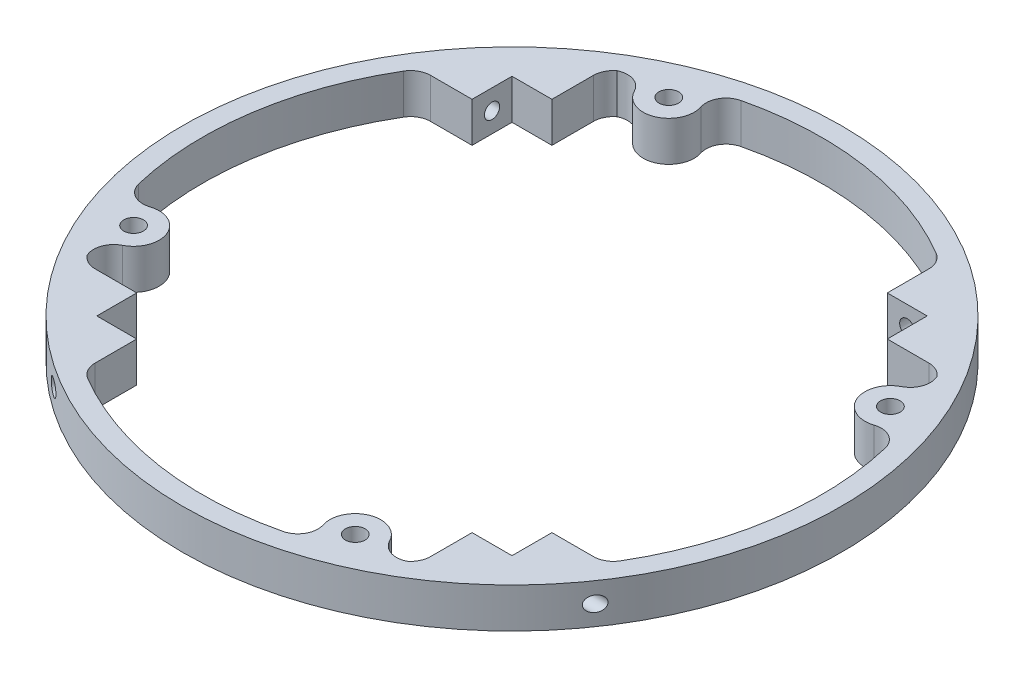
SolidWorks part; units mm, degrees
material "6061-T6 (SS)"
ref_plane "Front Plane" through (0, 0, 0) normal (0, 0, 1) x (1, 0, 0)
ref_plane "Top Plane" through (0, 0, 0) normal (0, 1, 0) x (1, 0, 0)
ref_plane "Right Plane" through (0, 0, 0) normal (1, 0, 0) x (0, 0, -1)
sketch "Sketch1" plane through (0, 0, 0) normal (0, 1, 0) x (1, 0, 0)
  line L0 (0, 0) -> (0, 84.2831) construction
  line L1 (-52, 52) -> (52, 52) construction
  line L2 (-52, 52) -> (-52, -52) construction
  line L3 (-52, -52) -> (52, -52) construction
  line L4 (52, 52) -> (52, -52) construction
  line L5 (0, 0) -> (-99.9306, 0) construction
  line L6 (0, 0) -> (-52, 52) construction
  line L7 (0, 0) -> (-31.8699, 76.9407) construction
  line L8 (-42, 52) -> (-52, 52)
  line L9 (-52, 52) -> (-52, 42)
  line L10 (-52, 42) -> (-65.192, 42)
  line L11 (-42, 52) -> (-42, 65.192)
  line L12 (-35.4887, 68.9533) -> (-33.6765, 64.5783)
  line L13 (-23.663, 73.8516) -> (-21.8509, 69.4766)
  line L14 (42, 52) -> (42, 65.192)
  line L15 (52, 52) -> (42, 52)
  line L16 (52, 42) -> (52, 52)
  line L17 (52, 42) -> (65.192, 42)
  line L18 (68.9533, 35.4887) -> (64.5783, 33.6765)
  line L19 (73.8516, 23.663) -> (69.4766, 21.8509)
  line L20 (52, -42) -> (65.192, -42)
  line L21 (52, -52) -> (52, -42)
  line L22 (42, -52) -> (52, -52)
  line L23 (42, -52) -> (42, -65.192)
  line L24 (35.4887, -68.9533) -> (33.6765, -64.5783)
  line L25 (23.663, -73.8516) -> (21.8509, -69.4766)
  line L26 (-42, -52) -> (-42, -65.192)
  line L27 (-52, -52) -> (-42, -52)
  line L28 (-52, -42) -> (-52, -52)
  line L29 (-52, -42) -> (-65.192, -42)
  line L30 (-68.9533, -35.4887) -> (-64.5783, -33.6765)
  line L31 (-73.8516, -23.663) -> (-69.4766, -21.8509)
  circle A0 centre (0, 0) radius 82.55
  arc A1 (-65.192, 42) -> (-77.55, 0) centre (0, 0) ccw
  arc A2 (-42, 65.192) -> (-35.4887, 68.9533) centre (0, 0) cw
  arc A3 (-33.6765, 64.5783) -> (-21.8509, 69.4766) centre (-27.7637, 67.0275) ccw
  arc A4 (0, 77.55) -> (-23.663, 73.8516) centre (0, 0) ccw
  arc A5 (42, 65.192) -> (0, 77.55) centre (0, 0) ccw
  arc A6 (65.192, 42) -> (68.9533, 35.4887) centre (0, 0) cw
  arc A7 (64.5783, 33.6765) -> (69.4766, 21.8509) centre (67.0275, 27.7637) ccw
  arc A8 (77.55, 0) -> (73.8516, 23.663) centre (0, 0) ccw
  arc A9 (65.192, -42) -> (77.55, 0) centre (0, 0) ccw
  arc A10 (42, -65.192) -> (35.4887, -68.9533) centre (0, 0) cw
  arc A11 (33.6765, -64.5783) -> (21.8509, -69.4766) centre (27.7637, -67.0275) ccw
  arc A12 (0, -77.55) -> (23.663, -73.8516) centre (0, 0) ccw
  arc A13 (-42, -65.192) -> (0, -77.55) centre (0, 0) ccw
  arc A14 (-65.192, -42) -> (-68.9533, -35.4887) centre (0, 0) cw
  arc A15 (-64.5783, -33.6765) -> (-69.4766, -21.8509) centre (-67.0275, -27.7637) ccw
  arc A16 (-77.55, 0) -> (-73.8516, -23.663) centre (0, 0) ccw
  point P21 (-22.7569, 71.6641)
  point P61 (0, 0)
  dimension "D1" = 165.1
  dimension "D2" = 104
  dimension "D3" = 22.5
  dimension "D4" = 5
  dimension "D5" = 72.55
  dimension "D6" = 12.8
  dimension "D7" = 10
  dimension "D8" = 4
extrude "Boss-Extrude1" add sketch "Sketch1" along normal blind 10
fillet "Fillet1" radius 5 16 edges at (-73.8516, 5, 23.663) (-68.9533, 5, 35.4887) (-42, 5, 65.192) (-65.192, 5, 42) (23.663, 5, 73.8516) (35.4887, 5, 68.9533) (42, 5, 65.192) (65.192, 5, 42) (73.8516, 5, -23.663) (68.9533, 5, -35.4887) (65.192, 5, -42) (42, 5, -65.192) (-35.4887, 5, -68.9533) (-23.663, 5, -73.8516) (-42, 5, -65.192) (-65.192, 5, -42)
hole_wizard "#10 (0.1935) Diameter Hole1" positions "Sketch4" profile "Sketch3" hole size "#10" standard "ANSI Inch" end condition through all
sketch "Sketch4" plane through (0, 10, 0) normal (0, 1, 0) x (1, 0, 0)
  point P0 (67.0275, 27.7637)
sketch "Sketch3" plane through (67.0275, 10, -27.7637) normal (1, 0, 0) x (0, 0, 1)
  line L0 (0, 0) -> (0, 10)
  line L1 (0, 10) -> (2.4574, 10)
  line L2 (2.4574, 10) -> (2.4574, 0)
  line L5 (2.4574, 0) -> (0, 0)
  line L11 (0, -6.35) -> (0, 107.95) construction
  dimension "Thru Hole Dia." = 4.9149
  dimension "Thru Hole Depth" = 10
hole_wizard "#10-24 Tapped Hole1" positions "Sketch8" profile "Sketch9" tap size "#10-24" standard "ANSI Inch" end condition through all
sketch "Sketch8" plane through (0, 0, -52) normal (0, 0, 1) x (1, 0, 0)
  line L0 (52, 0) -> (42, 10)
  point P0 (47, 5)
  point P10 (47, 5)
sketch "Sketch9" plane through (47, 5, -52) normal (1, 0, 0) x (0, -1, 0)
  line L0 (0, 0) -> (0, 30.55)
  line L1 (0, 30.55) -> (1.8986, 30.55)
  line L2 (1.8986, 30.55) -> (1.8986, 0)
  line L5 (1.8986, 0) -> (0, 0)
  line L11 (0, -6.35) -> (0, 107.95) construction
  dimension "Thru Tap Drill Dia." = 3.7973
  dimension "Thru Tap Drill Depth" = 30.55
cosmetic thread "Hole Thread2" parameters "D2"=4.826
ref_axis "Axis1" through (0, 10.5, 0) along (0, -1, 0)
pattern_circular "CirPattern1" count 4 over 360 about axis through (0, 10.5, 0) along (0, -1, 0) of "#10 (0.1935) Diameter Hole1", "#10-24 Tapped Hole1"
equation "\"TubeDiameter\" = 6.500in"
equation "\"D1@Sketch1\"=\"TubeDiameter\""
equation "\"D5@Sketch1\"=\"TubeDiameter\"/2-10mm"
